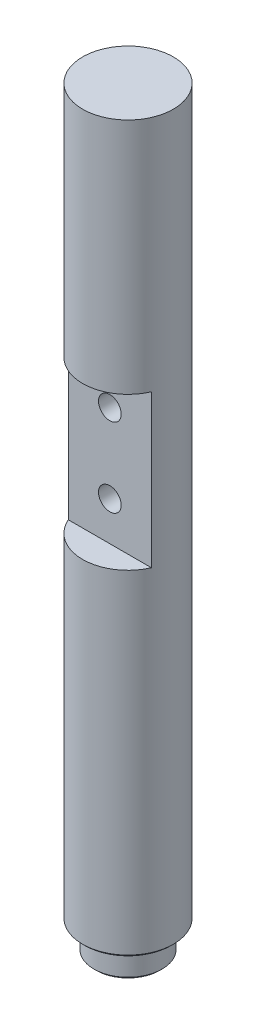
SolidWorks part; units mm, degrees
ref_plane "Front Plane" through (0, 0, 0) normal (0, 0, 1) x (1, 0, 0)
ref_plane "Top Plane" through (0, 0, 0) normal (0, 1, 0) x (1, 0, 0)
ref_plane "Right Plane" through (0, 0, 0) normal (1, 0, 0) x (0, 0, -1)
sketch "Sketch1" plane through (0, 0, 0) normal (0, 1, 0) x (1, 0, 0)
  circle A0 centre (0, 0) radius 12.7
  dimension "D1" = 25.4
extrude "Boss-Extrude1" add sketch "Sketch1" along normal blind 203.2
sketch "Sketch2" plane through (0, 0, 0) normal (0, -1, 0) x (-1, 0, 0)
  circle A0 centre (0, 0) radius 9.525
  dimension "D1" = 19.05
extrude "Boss-Extrude2" add sketch "Sketch2" along normal blind 7.62
chamfer "Chamfer1" distance 0.635 angle 45 2 edges at (0, 0, 12.7) (0, -7.62, -9.525)
sketch "Sketch4" plane through (0, 0, 0) normal (1, 0, 0) x (0, 0, -1)
  line L0 (-12.7, 203.2) -> (-12.7, 0.635) construction
  line L1 (-12.7, 136.652) -> (-5.08, 136.652)
  line L2 (-12.7, 136.652) -> (-12.7, 93.98)
  line L3 (-12.7, 93.98) -> (-5.08, 93.98)
  line L4 (-5.08, 136.652) -> (-5.08, 93.98)
  line L5 (-8.89, -7.62) -> (8.89, -7.62) construction
  dimension "D1" = 42.672
  dimension "D2" = 101.6
  dimension "D3" = 7.62
extrude "Cut-Extrude1" cut sketch "Sketch4" against normal blind 25.4 and the other way blind 25.4
sketch "Sketch5" plane through (0, 0, 5.08) normal (0, 0, 1) x (1, 0, 0)
  circle A0 centre (0, 104.902) radius 3.175
  circle A1 centre (0, 127) radius 3.175
  dimension "D1" = 6.35
  dimension "D2" = 10.922
  dimension "D3" = 33.02
extrude "Cut-Extrude2" cut sketch "Sketch5" against normal blind 25.4
